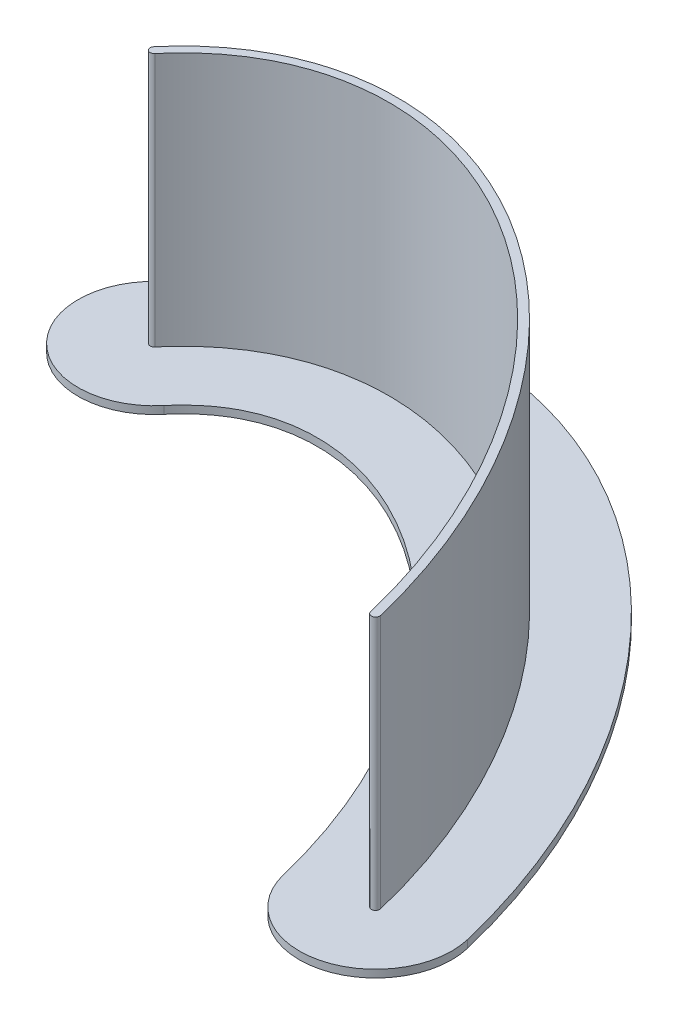
SolidWorks part; units mm, degrees
material "ABS"
ref_plane "Front Plane" through (0, 0, 0) normal (0, 0, 1) x (1, 0, 0)
ref_plane "Top Plane" through (0, 0, 0) normal (0, 1, 0) x (1, 0, 0)
ref_plane "Right Plane"
other "Center of Mass"
sketch "Sketch1" plane through (0, 0, 0) normal (0, 1, 0) x (1, 0, 0)
  line L0 (275, 0) -> (-275, 0) construction
  line L1 (0, 275) -> (0, -275) construction
  line L2 (-182.0856, 171.3033) -> (-104.6313, 0) construction
  line L3 (-215.7962, -50.2629) -> (-163.5619, 130.3349) construction
  line L4 (-211.7245, 148.5052) -> (-163.5619, 130.3349) construction
  circle A0 centre (0, 0) radius 275
  circle A2 centre (0, 0) radius 250 construction
  arc A3 (25.4478, 0.3866) -> (22.2396, -0.3866) centre (23.8437, 0) cw
  arc A4 (-212.9894, 149.5647) -> (-210.4596, 147.4457) centre (-211.7245, 148.5052) ccw
  arc A5 (53.0088, 7.0286) -> (-5.3213, -7.0286) centre (23.8437, 0) cw
  arc A6 (-234.7226, 167.7688) -> (-188.7263, 129.2416) centre (-211.7245, 148.5052) ccw
  ellipse E0 centre (-104.6313, 0) end of major axis (-182.0856, 171.3033) minor radius 122 (23.8437, 0) -> (-211.7245, 148.5052) ccw construction
  spline S0 degree 1 poles (25.4478, 0.3866) (-212.9894, 149.5647) knots 0 0 1 1 construction
  spline S1 degree 3 poles (25.4478, 0.3866) (24.4694, 4.4463) (22.3332, 12.4961) (17.279, 28.592) (9.5756, 48.4089) (-1.7321, 71.3257) (-19.2829, 100.1648) (-45.2855, 132.0102) (-80.7879, 160.7412) (-111.8662, 175.0391) (-136.3105, 180.0466) (-154.1015, 180.5133) (-171.017, 177.6633) (-184.1086, 172.5608) (-193.8245, 166.9017) (-200.6969, 161.8922) (-206.0539, 157.0976) (-210.0961, 152.9122) (-212.0449, 150.6923) (-212.9894, 149.5647) knots 1.285392 1.285392 1.285392 1.285392 1.352866 1.42034 1.555288 1.690236 1.825184 2.09508 2.364976 2.634872 2.76982 2.904768 3.039716 3.174664 3.242138 3.309612 3.377086 3.410823 3.44456 3.44456 3.44456 3.44456
  spline S2 degree 1 poles (22.2396, -0.3866) (-210.4596, 147.4457) knots 0 0 1 1 construction
  spline S3 degree 3 poles (22.2396, -0.3866) (21.7575, 1.6142) (20.7491, 5.5973) (18.536, 13.5746) (14.1687, 27.4797) (6.5508, 47.0799) (-4.6284, 69.7349) (-21.9756, 98.2395) (-47.6513, 129.6778) (-82.5919, 157.9389) (-112.9814, 171.8989) (-136.7062, 176.7531) (-153.8827, 177.1998) (-170.1398, 174.4575) (-182.6931, 169.5643) (-192.0151, 164.135) (-198.6163, 159.3236) (-203.7713, 154.7102) (-207.6668, 150.6769) (-209.5482, 148.5338) (-210.4596, 147.4457) knots 1.285392 1.285392 1.285392 1.285392 1.319129 1.352866 1.42034 1.555288 1.690236 1.825184 2.09508 2.364976 2.634872 2.76982 2.904768 3.039716 3.174664 3.242138 3.309612 3.377086 3.410823 3.44456 3.44456 3.44456 3.44456
  spline S4 degree 1 poles (53.0088, 7.0286) (-234.7226, 167.7688) knots 0 0 1 1 construction
  spline S5 degree 3 poles (53.0088, 7.0286) (51.9298, 11.5056) (49.5718, 20.3909) (44.0124, 38.0933) (35.5564, 59.844) (23.1512, 84.9869) (3.8493, 116.7076) (-24.9605, 152.0472) (-65.2906, 184.8159) (-102.2851, 202.0165) (-132.9109, 208.3406) (-155.9812, 208.9799) (-178.5521, 205.2033) (-199.8132, 196.9242) (-215.7373, 186.4968) (-227.0775, 176.3422) (-232.2692, 170.6978) (-234.7226, 167.7688) knots 1.285392 1.285392 1.285392 1.285392 1.352866 1.42034 1.555288 1.690236 1.825184 2.09508 2.364976 2.634872 2.76982 2.904768 3.039716 3.174664 3.309612 3.377086 3.44456 3.44456 3.44456 3.44456
  spline S6 degree 1 poles (-5.3213, -7.0286) (-188.7263, 129.2416) knots 0 0 1 1 construction
  spline S7 degree 3 poles (-5.3213, -7.0286) (-5.753, -5.2375) (-6.655, -1.6741) (-8.6399, 5.4809) (-11.4431, 14.4066) (-15.3105, 25.0452) (-21.1104, 39.0495) (-29.5117, 56.0737) (-45.1078, 81.6966) (-67.9763, 109.6408) (-98.0892, 133.8643) (-122.5625, 144.9216) (-140.1057, 148.4591) (-152.0031, 148.7333) (-162.6045, 146.9172) (-170.5326, 143.8223) (-176.4709, 140.3668) (-180.7423, 137.257) (-184.1617, 134.2004) (-186.7975, 131.4729) (-188.0993, 129.9903) (-188.7263, 129.2416) knots 1.285392 1.285392 1.285392 1.285392 1.319129 1.352866 1.42034 1.487814 1.555288 1.690236 1.825184 2.09508 2.364976 2.634872 2.76982 2.904768 3.039716 3.174664 3.242138 3.309612 3.377086 3.410823 3.44456 3.44456 3.44456 3.44456
  point P6 (0, 0)
  point P14 (0, 0)
  point P17 (-250, 0)
  dimension "rotor_diameter" = 500
  dimension "rotor_diameter_external" = 550
  dimension "elli_minor_radius" = 122
  dimension "elli_mayor_radius" = 188
  dimension "cut_angle" = 45
  dimension "half_overlap" = 23.8437
  dimension "blade_thickness" = 3.3
  dimension "D9" = 267.8651
  dimension "D6" = 238.4372
  dimension "D1" = 30
  dimension "D2" = 30
extrude "Aspa" add sketch "Sketch1" along normal blind 100 contours S3 A4 S1 A3
extrude "Boss-Extrude1" add sketch "Sketch1<6>" against normal blind 3 contours S5 A6 S7 A5
sketch "Sketch1<6>" plane through (0, 0, 0) normal (0, 1, 0) x (1, 0, 0) same geometry as "Sketch1"
equation "\"cut_angle\"= 45deg'Anglulo de corte"
equation "\"elli_mayor_radius\"= 188mm'Radio mayor de la elipse"
equation "\"elli_minor_radius\"= 122mm'Radio menor de la elipse"
equation "\"elli_chord\"= \"D6@Sketch1\"'Cuerda de la elipse"
equation "\"overlap_percent\"= 20'Porcentaje de superposicion"
equation "\"half_overlap@Sketch1\"= \"D6@Sketch1\" * \"overlap_percent\" / 200"
equation "\"overlap_distance\"= \"half_overlap@Sketch1\" * 2'Distancia de superposicion"
equation "\"rotor_diameter\"= 500mm'Diametro del rotor"
equation "\"blade_quantity\"= 2'Cantidad de aspas"
equation "\"rotor_height\"= 536.8mm'Altura del rotor"
equation "\"blade_thickness\"= 3.3mm'Espesor de las aspas"
equation "\"blade_pattern_angle\"= 180deg 'Angulo de repeticion de aspa"
equation "\"blade_torsion_angle\"= 0deg'Angulo de torsion del aspa"
equation "\"aspect_ratio\"= 1.17'Relación de aspecto de la helice"
equation "\"rotor_diameter_external@Sketch1\"= \"rotor_diameter\" * 1.1"
equation "\"rotor_diameter@Sketch1\"= \"rotor_diameter\""
equation "\"elli_minor_radius@Sketch1\"= \"elli_minor_radius\""
equation "\"elli_mayor_radius@Sketch1\"= \"elli_mayor_radius\""
equation "\"cut_angle@Sketch1\"= \"cut_angle\""
equation "\"blade_thickness@Sketch1\"= \"blade_thickness\""
equation "\"rotor_height@Aspa\"=100mm"
equation "\"blade_quantity@CirPattern1\"= \"blade_quantity\""
equation "\"blade_angle@CirPattern1\"=\"blade_pattern_angle\""
equation "\"D0@Flex2\"= \"blade_torsion_angle\""
equation "\"D1@Plane1\" = \"rotor_height@Aspa\" / 2 - 1"
equation "\"D1@Sketch7\" = \"rotor_diameter_external@Sketch1\""
